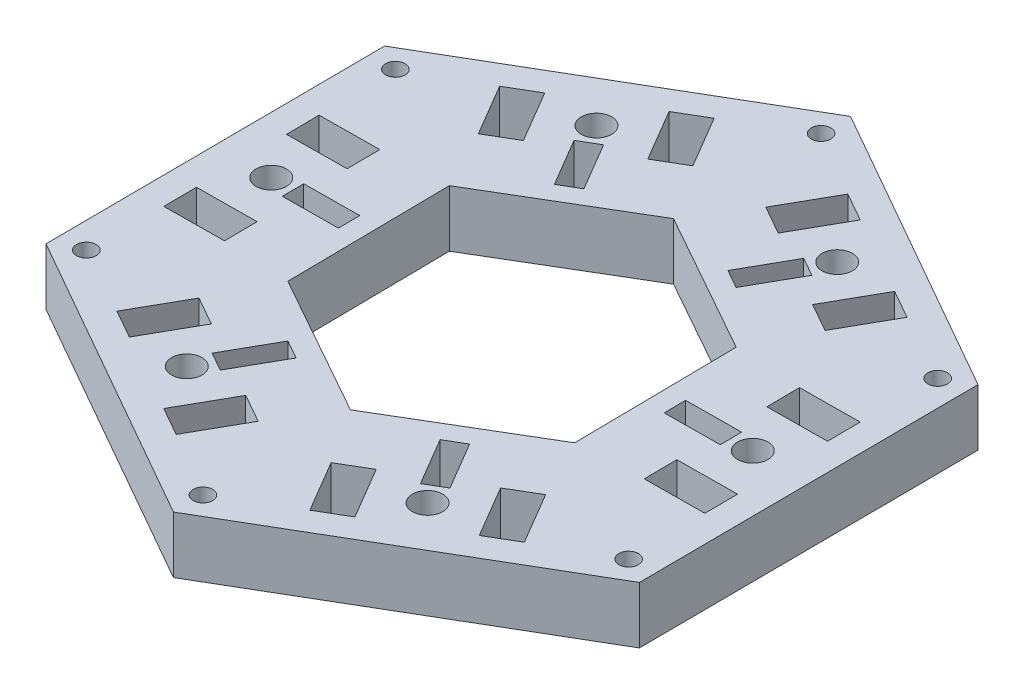
SolidWorks part; units mm, degrees
ref_plane "Front Plane" through (0, 0, 0) normal (0, 0, 1) x (1, 0, 0)
ref_plane "Top Plane" through (0, 0, 0) normal (0, 1, 0) x (1, 0, 0)
ref_plane "Right Plane" through (0, 0, 0) normal (1, 0, 0) x (0, 0, -1)
sketch "Sketch1" plane through (0, 0, 0) normal (0, 1, 0) x (1, 0, 0)
  line L0 (3.826, 24.5664) -> (7.0318, 22.7534)
  line L7 (21.8831, 12.8954) -> (-0.2262, 25.399)
  line L8 (-0.2262, 25.399) -> (-22.1093, 12.5036)
  line L9 (-22.1093, 12.5036) -> (-21.8831, -12.8954)
  line L10 (-21.8831, -12.8954) -> (0.2262, -25.399)
  line L11 (0.2262, -25.399) -> (22.1093, -12.5036)
  line L12 (22.1093, -12.5036) -> (21.8831, 12.8954)
  line L13 (32.8819, 19.2455) -> (-0.2262, 38.0993)
  line L14 (-0.2262, 38.0993) -> (-33.1081, 18.8538)
  line L15 (-33.1081, 18.8538) -> (-32.8819, -19.2455)
  line L16 (-32.8819, -19.2455) -> (0.2262, -38.0993)
  line L17 (0.2262, -38.0993) -> (33.1081, -18.8538)
  line L18 (33.1081, -18.8538) -> (32.8819, 19.2455)
  line L19 (10.3453, 28.6123) -> (7.0318, 22.7534)
  line L20 (7.1394, 30.4253) -> (10.3453, 28.6123)
  line L25 (-10.8531, 28.4236) -> (-7.4359, 22.6245)
  line L26 (-7.6801, 30.2934) -> (-10.8531, 28.4236)
  line L27 (-4.2628, 24.4944) -> (-7.6801, 30.2934)
  line L30 (3.826, 24.5664) -> (7.1394, 30.4253)
  line L31 (15.8755, 17.7519) -> (19.0813, 15.9389)
  line L32 (19.0813, 15.9389) -> (22.3948, 21.7978)
  line L33 (22.3948, 21.7978) -> (19.189, 23.6109)
  line L34 (19.189, 23.6109) -> (15.8755, 17.7519)
  line L35 (23.1881, 8.9698) -> (23.2209, 5.287)
  line L36 (29.9516, 5.3469) -> (23.2209, 5.287)
  line L37 (29.9188, 9.0298) -> (29.9516, 5.3469)
  line L38 (23.1881, 8.9698) -> (29.9188, 9.0298)
  line L39 (-11.1677, 18.9513) -> (-15.939, 27.0481) construction
  line L40 (-0.2262, 25.399) -> (-2.4173, 29.1173) construction
  line L41 (-19.3621, 15.5966) -> (-16.1891, 17.4664)
  line L44 (-19.3621, 15.5966) -> (-22.7794, 21.3956)
  line L45 (-22.7794, 21.3956) -> (-19.6064, 23.2654)
  line L46 (-19.6064, 23.2654) -> (-16.1891, 17.4664)
  line L49 (-7.4359, 22.6245) -> (-4.2628, 24.4944)
  line L50 (23.3114, -4.8726) -> (23.3441, -8.5555)
  line L51 (23.3441, -8.5555) -> (30.0749, -8.4956)
  line L52 (30.0749, -8.4956) -> (30.0421, -4.8127)
  line L53 (30.0421, -4.8127) -> (23.3114, -4.8726)
  line L54 (19.3621, -15.5966) -> (16.1891, -17.4664)
  line L55 (19.6064, -23.2654) -> (16.1891, -17.4664)
  line L56 (22.7794, -21.3956) -> (19.6064, -23.2654)
  line L57 (19.3621, -15.5966) -> (22.7794, -21.3956)
  line L58 (7.4359, -22.6245) -> (4.2628, -24.4944)
  line L59 (4.2628, -24.4944) -> (7.6801, -30.2934)
  line L60 (7.6801, -30.2934) -> (10.8531, -28.4236)
  line L61 (10.8531, -28.4236) -> (7.4359, -22.6245)
  line L62 (-3.826, -24.5664) -> (-7.0318, -22.7534)
  line L63 (-10.3453, -28.6123) -> (-7.0318, -22.7534)
  line L64 (-7.1394, -30.4253) -> (-10.3453, -28.6123)
  line L65 (-3.826, -24.5664) -> (-7.1394, -30.4253)
  line L66 (-15.8755, -17.7519) -> (-19.0813, -15.9389)
  line L67 (-19.0813, -15.9389) -> (-22.3948, -21.7978)
  line L68 (-22.3948, -21.7978) -> (-19.189, -23.6109)
  line L69 (-19.189, -23.6109) -> (-15.8755, -17.7519)
  line L70 (-23.1881, -8.9698) -> (-23.2209, -5.287)
  line L71 (-29.9516, -5.3469) -> (-23.2209, -5.287)
  line L72 (-29.9188, -9.0298) -> (-29.9516, -5.3469)
  line L73 (-23.1881, -8.9698) -> (-29.9188, -9.0298)
  line L74 (-23.3114, 4.8726) -> (-23.3441, 8.5555)
  line L75 (-23.3441, 8.5555) -> (-30.0749, 8.4956)
  line L76 (-30.0749, 8.4956) -> (-30.0421, 4.8127)
  line L77 (-30.0421, 4.8127) -> (-23.3114, 4.8726)
  line L102 (-13.3677, 20.3083) -> (-11.2888, 21.5333)
  line L103 (-11.2888, 21.5333) -> (-8.1295, 16.172)
  line L104 (-8.1295, 16.172) -> (-10.2084, 14.9469)
  line L105 (-10.2084, 14.9469) -> (-13.3677, 20.3083)
  line L106 (10.9036, 21.7309) -> (13.004, 20.5431)
  line L107 (13.004, 20.5431) -> (9.9406, 15.1263)
  line L108 (9.9406, 15.1263) -> (7.8402, 16.3142)
  line L109 (7.8402, 16.3142) -> (10.9036, 21.7309)
  line L110 (24.2713, 1.4227) -> (24.2928, -0.9902)
  line L111 (24.2928, -0.9902) -> (18.0701, -1.0456)
  line L112 (18.0701, -1.0456) -> (18.0486, 1.3673)
  line L113 (18.0486, 1.3673) -> (24.2713, 1.4227)
  line L114 (13.3677, -20.3083) -> (11.2888, -21.5333)
  line L115 (11.2888, -21.5333) -> (8.1295, -16.172)
  line L116 (8.1295, -16.172) -> (10.2084, -14.9469)
  line L117 (10.2084, -14.9469) -> (13.3677, -20.3083)
  line L118 (-10.9036, -21.7309) -> (-13.004, -20.5431)
  line L119 (-13.004, -20.5431) -> (-9.9406, -15.1263)
  line L120 (-9.9406, -15.1263) -> (-7.8402, -16.3142)
  line L121 (-7.8402, -16.3142) -> (-10.9036, -21.7309)
  line L122 (-24.2713, -1.4227) -> (-24.2928, 0.9902)
  line L123 (-24.2928, 0.9902) -> (-18.0701, 1.0456)
  line L124 (-18.0701, 1.0456) -> (-18.0486, -1.3673)
  line L125 (-18.0486, -1.3673) -> (-24.2713, -1.4227)
  line L127 (15.7326, 9.3444) -> (-0.2262, 18.297)
  line L128 (-0.2262, 18.297) -> (-15.9587, 8.9526)
  line L129 (-15.9587, 8.9526) -> (-15.7326, -9.3444)
  line L130 (-15.7326, -9.3444) -> (0.2262, -18.297)
  line L131 (0.2262, -18.297) -> (15.9587, -8.9526)
  line L132 (15.9587, -8.9526) -> (15.7326, 9.3444)
  line L133 (-33.1081, 18.8538) -> (-22.1093, 12.5036) construction
  circle A0 centre (0, 0) radius 32.9956 construction
  circle A1 centre (0, 0) radius 21.997 construction
  circle A2 centre (-13.5533, 22.9997) radius 1.7
  circle A3 centre (13.1416, 23.2374) radius 1.7
  circle A4 centre (0, 0) radius 21.997 construction
  circle A5 centre (26.695, 0.2377) radius 1.7
  circle A6 centre (0, 0) radius 21.997 construction
  circle A7 centre (13.5533, -22.9997) radius 1.7
  circle A8 centre (0, 0) radius 21.997 construction
  circle A9 centre (-13.1416, -23.2374) radius 1.7
  circle A10 centre (0, 0) radius 21.997 construction
  circle A11 centre (-26.695, -0.2377) radius 1.7
  circle A12 centre (0, 0) radius 21.997 construction
  circle A13 centre (0, 0) radius 21.997 construction
  circle A14 centre (0, 0) radius 21.997 construction
  circle A15 centre (0, 0) radius 21.997 construction
  circle A16 centre (0, 0) radius 21.997 construction
  circle A17 centre (0, 0) radius 21.997 construction
  circle A18 centre (0, 0) radius 1.27
  circle A19 centre (0, 0) radius 21.997 construction
  circle A20 centre (0, 0) radius 21.997 construction
  circle A21 centre (0, 0) radius 21.997 construction
  circle A22 centre (0, 0) radius 21.997 construction
  circle A23 centre (0, 0) radius 21.997 construction
  circle A24 centre (0, 0) radius 15.8469 construction
  circle A25 centre (-30.2485, 17.2028) radius 1.0922
  circle A26 centre (-0.2262, 34.7973) radius 1.0922
  circle A27 centre (0, 0) radius 32.9956 construction
  circle A28 centre (30.0223, 17.5945) radius 1.0922
  circle A29 centre (0, 0) radius 32.9956 construction
  circle A30 centre (30.2485, -17.2028) radius 1.0922
  circle A31 centre (0, 0) radius 32.9956 construction
  circle A32 centre (0.2262, -34.7973) radius 1.0922
  circle A33 centre (0, 0) radius 32.9956 construction
  circle A34 centre (-30.0223, -17.5945) radius 1.0922
  circle A35 centre (0, 0) radius 32.9956 construction
  point P58 (-15.0363, 25.5162)
  point P88 (0, 0)
  point P89 (-12.3283, 20.9208)
  point P119 (0, 0)
  point P129 (0, 0)
  point P151 (0, 0)
  dimension "D17" = 3.4
  dimension "D6" = 3.4
  dimension "D13" = 2.286
  dimension "D19" = 2.54
  dimension "D21" = 2.1844
  dimension "D2" = 25.4
  dimension "D3" = 6
  dimension "D4" = 25.399
  dimension "D5" = 5.08
  dimension "D7" = 4.1368
  dimension "D8" = 6.731
  dimension "D9" = 3.683
  dimension "D10" = 3.302
  dimension "D11" = 1.27
  dimension "D12" = 6
  dimension "D14" = 6.223
  dimension "D15" = 6
  dimension "D18" = 6.3502
  dimension "D16" = 2.413
  dimension "D20" = 18.297
  dimension "D22" = 3.302
  dimension "D23" = 6
extrude "Boss-Extrude1" add sketch "Sketch1" against normal blind 6.35 contours L17 L18 L13 L14 L15 L16 A34 A32 A30 A28 A26 A25 A11 A9 A7 A5 A3 A2 L77 L76 L75 L74 L69 L68 L67 L66 L61 L60 L59 L58 L53 L52 L51 L50 | L124 L125 L9 L10 L119 L120 L121 L11 L115 L116 L117 L12 L111 L112 L113 L7 L107 L108 L109 L8 L103 L104 L105 L123 L132 L131 L130 L129 L128 L127 region at (21.2608, 0, -7.1428) region at (31.9855, 0, -0.1899)
